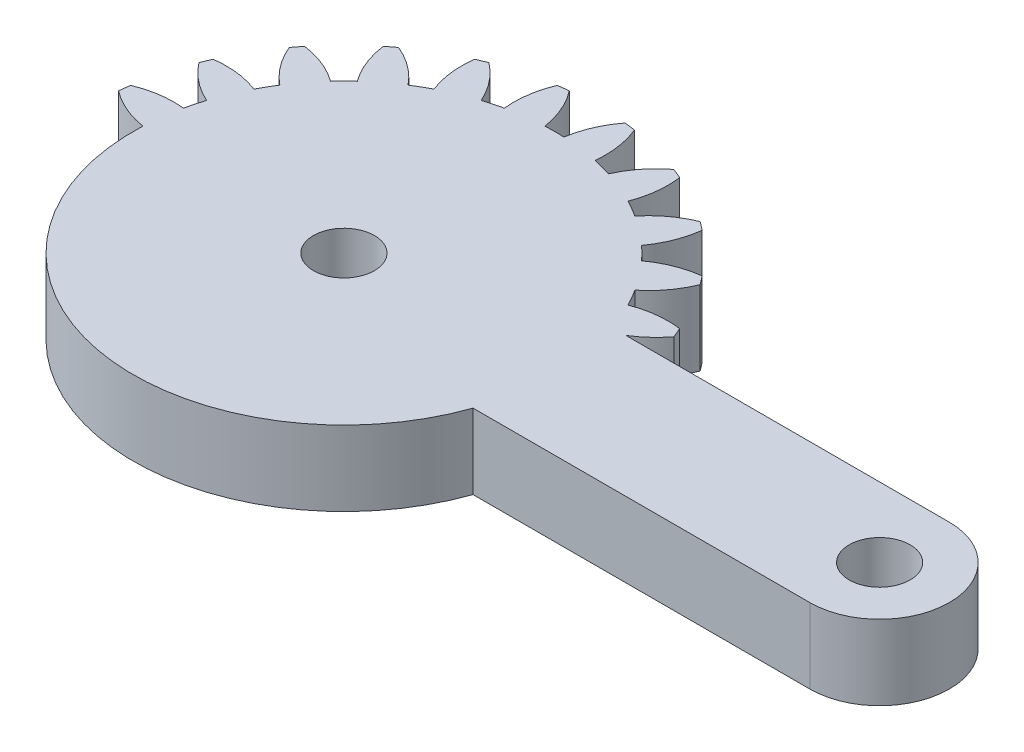
SolidWorks part; units mm, degrees
ref_plane "Front Plane" through (0, 0, 0) normal (0, 0, 1) x (1, 0, 0)
ref_plane "Top Plane" through (0, 0, 0) normal (0, 1, 0) x (1, 0, 0)
ref_plane "Right Plane" through (0, 0, 0) normal (1, 0, 0) x (0, 0, -1)
sketch "Sketch1" plane through (0, 0, 0) normal (0, 1, 0) x (1, 0, 0)
  line L0 (20.6437, 4) -> (2.0816, 4)
  line L1 (2.0816, -4) -> (20.6437, -4)
  arc A0 (2.0816, 4) -> (3.5217, 5.3071) centre (-0.7683, 8.5867) ccw
  arc A1 (3.5217, 5.3071) -> (3.2829, 5.8838) centre (-10.1063, 0) ccw
  arc A2 (3.2829, 5.8838) -> (0.6271, 5.5703) centre (2.5684, 0.5313) ccw
  arc A3 (0.6271, 5.5703) -> (0.0844, 6.5103) centre (-10.1063, 0) ccw
  arc A4 (0.0844, 6.5103) -> (1.6838, 8.6535) centre (-3.3089, 10.711) ccw
  arc A5 (1.6838, 8.6535) -> (1.3038, 9.1487) centre (-10.1063, 0) ccw
  arc A6 (1.3038, 9.1487) -> (-1.1803, 8.1585) centre (1.999, 3.7936) ccw
  arc A7 (-1.1803, 8.1585) -> (-1.9479, 8.926) centre (-10.1063, 0) ccw
  arc A8 (-1.9479, 8.926) -> (-0.9576, 11.4102) centre (-6.3127, 12.1053) ccw
  arc A9 (-0.9576, 11.4102) -> (-1.4528, 11.7901) centre (-10.1063, 0) ccw
  arc A10 (-1.4528, 11.7901) -> (-3.596, 10.1907) centre (0.6046, 6.7975) ccw
  arc A11 (-3.596, 10.1907) -> (-4.5361, 10.7334) centre (-10.1063, 0) ccw
  arc A12 (-4.5361, 10.7334) -> (-4.2225, 13.3892) centre (-9.5751, 12.6747) ccw
  arc A13 (-4.2225, 13.3892) -> (-4.7992, 13.6281) centre (-10.1063, 0) ccw
  arc A14 (-4.7992, 13.6281) -> (-6.4554, 11.5285) centre (-1.5196, 9.3381) ccw
  arc A15 (-6.4554, 11.5285) -> (-7.5039, 11.8094) centre (-10.1063, 0) ccw
  arc A16 (-7.5039, 11.8094) -> (-7.8884, 14.4558) centre (-12.8736, 12.3803) ccw
  arc A17 (-7.8884, 14.4558) -> (-8.5072, 14.5373) centre (-10.1063, 0) ccw
  arc A18 (-8.5072, 14.5373) -> (-9.5636, 12.0806) centre (-4.2291, 11.2423) ccw
  arc A19 (-9.5636, 12.0806) -> (-10.6491, 12.0806) centre (-10.1063, 0) ccw
  arc A20 (-10.6491, 12.0806) -> (-11.7054, 14.5373) centre (-15.9836, 11.2423) ccw
  arc A21 (-11.7054, 14.5373) -> (-12.3243, 14.4558) centre (-10.1063, 0) ccw
  arc A22 (-12.3243, 14.4558) -> (-12.7088, 11.8094) centre (-7.3391, 12.3803) ccw
  arc A23 (-12.7088, 11.8094) -> (-13.7573, 11.5285) centre (-10.1063, 0) ccw
  arc A24 (-13.7573, 11.5285) -> (-15.4135, 13.6281) centre (-18.6931, 9.3381) ccw
  arc A25 (-15.4135, 13.6281) -> (-15.9901, 13.3892) centre (-10.1063, 0) ccw
  arc A26 (-15.9901, 13.3892) -> (-15.6766, 10.7334) centre (-10.6376, 12.6747) ccw
  arc A27 (-15.6766, 10.7334) -> (-16.6166, 10.1907) centre (-10.1063, 0) ccw
  arc A28 (-16.6166, 10.1907) -> (-18.7599, 11.7901) centre (-20.8173, 6.7975) ccw
  arc A29 (-18.7599, 11.7901) -> (-19.255, 11.4102) centre (-10.1063, 0) ccw
  arc A30 (-19.255, 11.4102) -> (-18.2648, 8.926) centre (-13.9, 12.1053) ccw
  arc A31 (-18.2648, 8.926) -> (-19.0324, 8.1585) centre (-10.1063, 0) ccw
  arc A32 (-19.0324, 8.1585) -> (-21.5165, 9.1487) centre (-22.2117, 3.7936) ccw
  arc A33 (-21.5165, 9.1487) -> (-21.8965, 8.6535) centre (-10.1063, 0) ccw
  arc A34 (-21.8965, 8.6535) -> (-20.2971, 6.5103) centre (-16.9038, 10.711) ccw
  arc A35 (-20.2971, 6.5103) -> (-20.8398, 5.5703) centre (-10.1063, 0) ccw
  arc A36 (-20.8398, 5.5703) -> (-23.4956, 5.8838) centre (-22.7811, 0.5313) ccw
  arc A37 (-23.4956, 5.8838) -> (-23.7344, 5.3071) centre (-10.1063, 0) ccw
  arc A38 (-23.7344, 5.3071) -> (-21.6348, 3.6509) centre (-19.4444, 8.5867) ccw
  arc A39 (-21.6348, 3.6509) -> (-21.9157, 2.6025) centre (-10.1063, 0) ccw
  arc A40 (-21.9157, 2.6025) -> (-24.5622, 2.2179) centre (-22.4867, -2.7673) ccw
  arc A41 (-24.5622, 2.2179) -> (-24.6437, 1.5991) centre (-10.1063, 0) ccw
  arc A42 (-24.6437, 1.5991) -> (-22.1869, 0.5427) centre (-21.3486, 5.8773) ccw
  arc A43 (-22.1869, 0.5427) -> (-22.1869, -0.5427) centre (-10.1063, 0) ccw
  arc A44 (-22.1869, -0.5427) -> (-24.6437, -1.5991) centre (-21.3486, -5.8773) ccw
  arc A45 (-24.6437, -1.5991) -> (-24.5622, -2.2179) centre (-10.1063, 0) ccw
  arc A46 (-24.5622, -2.2179) -> (-21.9157, -2.6025) centre (-22.4867, 2.7673) ccw
  arc A47 (-21.9157, -2.6025) -> (-21.6348, -3.6509) centre (-10.1063, 0) ccw
  arc A48 (-21.6348, -3.6509) -> (-23.7344, -5.3071) centre (-19.4444, -8.5867) ccw
  arc A49 (-23.7344, -5.3071) -> (-23.4956, -5.8838) centre (-10.1063, 0) ccw
  arc A50 (-23.4956, -5.8838) -> (-20.8398, -5.5703) centre (-22.7811, -0.5313) ccw
  arc A51 (-20.8398, -5.5703) -> (-20.2971, -6.5103) centre (-10.1063, 0) ccw
  arc A52 (-20.2971, -6.5103) -> (-21.8965, -8.6535) centre (-16.9038, -10.711) ccw
  arc A53 (-21.8965, -8.6535) -> (-21.5165, -9.1487) centre (-10.1063, 0) ccw
  arc A54 (-21.5165, -9.1487) -> (-19.0324, -8.1585) centre (-22.2117, -3.7936) ccw
  arc A55 (-19.0324, -8.1585) -> (-18.2648, -8.926) centre (-10.1063, 0) ccw
  arc A56 (-18.2648, -8.926) -> (-19.255, -11.4102) centre (-13.9, -12.1053) ccw
  arc A57 (-19.255, -11.4102) -> (-18.7599, -11.7901) centre (-10.1063, 0) ccw
  arc A58 (-18.7599, -11.7901) -> (-16.6166, -10.1907) centre (-20.8173, -6.7975) ccw
  arc A59 (-16.6166, -10.1907) -> (-15.6766, -10.7334) centre (-10.1063, 0) ccw
  arc A60 (-15.6766, -10.7334) -> (-15.9901, -13.3892) centre (-10.6376, -12.6747) ccw
  arc A61 (-15.9901, -13.3892) -> (-15.4135, -13.6281) centre (-10.1063, 0) ccw
  arc A62 (-15.4135, -13.6281) -> (-13.7573, -11.5285) centre (-18.6931, -9.3381) ccw
  arc A63 (-13.7573, -11.5285) -> (-12.7088, -11.8094) centre (-10.1063, 0) ccw
  arc A64 (-12.7088, -11.8094) -> (-12.3243, -14.4558) centre (-7.3391, -12.3803) ccw
  arc A65 (-12.3243, -14.4558) -> (-11.7054, -14.5373) centre (-10.1063, 0) ccw
  arc A66 (-11.7054, -14.5373) -> (-10.6491, -12.0806) centre (-15.9836, -11.2423) ccw
  arc A67 (-10.6491, -12.0806) -> (-9.5636, -12.0806) centre (-10.1063, 0) ccw
  arc A68 (-9.5636, -12.0806) -> (-8.5072, -14.5373) centre (-4.2291, -11.2423) ccw
  arc A69 (-8.5072, -14.5373) -> (-7.8884, -14.4558) centre (-10.1063, 0) ccw
  arc A70 (-7.8884, -14.4558) -> (-7.5039, -11.8094) centre (-12.8736, -12.3803) ccw
  arc A71 (-7.5039, -11.8094) -> (-6.4554, -11.5285) centre (-10.1063, 0) ccw
  arc A72 (-6.4554, -11.5285) -> (-4.7992, -13.6281) centre (-1.5196, -9.3381) ccw
  arc A73 (-4.7992, -13.6281) -> (-4.2225, -13.3892) centre (-10.1063, 0) ccw
  arc A74 (-4.2225, -13.3892) -> (-4.5361, -10.7334) centre (-9.5751, -12.6747) ccw
  arc A75 (-4.5361, -10.7334) -> (-3.596, -10.1907) centre (-10.1063, 0) ccw
  arc A76 (-3.596, -10.1907) -> (-1.4528, -11.7901) centre (0.6046, -6.7975) ccw
  arc A77 (-1.4528, -11.7901) -> (-0.9576, -11.4102) centre (-10.1063, 0) ccw
  arc A78 (-0.9576, -11.4102) -> (-1.9479, -8.926) centre (-6.3127, -12.1053) ccw
  arc A79 (-1.9479, -8.926) -> (-1.1803, -8.1585) centre (-10.1063, 0) ccw
  arc A80 (-1.1803, -8.1585) -> (1.3038, -9.1487) centre (1.999, -3.7936) ccw
  arc A81 (1.3038, -9.1487) -> (1.6838, -8.6535) centre (-10.1063, 0) ccw
  arc A82 (1.6838, -8.6535) -> (0.0844, -6.5103) centre (-3.3089, -10.711) ccw
  arc A83 (0.0844, -6.5103) -> (0.6271, -5.5703) centre (-10.1063, 0) ccw
  arc A84 (0.6271, -5.5703) -> (3.2829, -5.8838) centre (2.5684, -0.5313) ccw
  arc A85 (3.2829, -5.8838) -> (3.5217, -5.3071) centre (-10.1063, 0) ccw
  arc A86 (3.5217, -5.3071) -> (2.0816, -4) centre (-0.7683, -8.5867) ccw
  arc A87 (20.6437, -4) -> (20.6437, 4) centre (20.6437, 0) ccw
  circle A88 centre (-10.1063, 0) radius 1.75
  circle A89 centre (20.6437, 0) radius 1.75
  point P180 (0, 0)
  dimension "D1" = 3.5
  dimension "D2" = 3.5
  dimension "D3" = 0.6242
  dimension "D4" = 1.0854
  dimension "D5" = 12.0806
extrude "Boss-Extrude1" add sketch "Sketch1" along normal blind 4.3
sketch "Sketch2" plane through (0, 4.3, 0) normal (0, 1, 0) x (1, 0, 0)
  line L0 (2.0816, -4) -> (1.3057, -4)
  line L2 (20.6437, 4) -> (2.0816, 4)
  line L3 (2.0816, -4) -> (20.6437, -4)
  line L4 (20.6437, 4) -> (2.0816, 4)
  line L5 (2.0816, -4) -> (20.6437, -4)
  circle A0 centre (-10.1063, 0) radius 12.0927
  arc A88 (20.6437, -4) -> (20.6437, 4) centre (20.6437, 0) ccw
  arc A89 (2.0816, 4) -> (3.5217, 5.3071) centre (-0.7683, 8.5867) ccw
  arc A90 (3.5217, 5.3071) -> (3.2829, 5.8838) centre (-10.1063, 0) ccw
  arc A91 (3.2829, 5.8838) -> (0.6271, 5.5703) centre (2.5684, 0.5313) ccw
  arc A92 (0.6271, 5.5703) -> (0.0844, 6.5103) centre (-10.1063, 0) ccw
  arc A93 (0.0844, 6.5103) -> (1.6838, 8.6535) centre (-3.3089, 10.711) ccw
  arc A94 (1.6838, 8.6535) -> (1.3038, 9.1487) centre (-10.1063, 0) ccw
  arc A95 (1.3038, 9.1487) -> (-1.1803, 8.1585) centre (1.999, 3.7936) ccw
  arc A96 (-1.1803, 8.1585) -> (-1.9479, 8.926) centre (-10.1063, 0) ccw
  arc A97 (-1.9479, 8.926) -> (-0.9576, 11.4102) centre (-6.3127, 12.1053) ccw
  arc A98 (-0.9576, 11.4102) -> (-1.4528, 11.7901) centre (-10.1063, 0) ccw
  arc A99 (-1.4528, 11.7901) -> (-3.596, 10.1907) centre (0.6046, 6.7975) ccw
  arc A100 (-3.596, 10.1907) -> (-4.5361, 10.7334) centre (-10.1063, 0) ccw
  arc A101 (-4.5361, 10.7334) -> (-4.2225, 13.3892) centre (-9.5751, 12.6747) ccw
  arc A102 (-4.2225, 13.3892) -> (-4.7992, 13.6281) centre (-10.1063, 0) ccw
  arc A103 (-4.7992, 13.6281) -> (-6.4554, 11.5285) centre (-1.5196, 9.3381) ccw
  arc A104 (-6.4554, 11.5285) -> (-7.5039, 11.8094) centre (-10.1063, 0) ccw
  arc A105 (-7.5039, 11.8094) -> (-7.8884, 14.4558) centre (-12.8736, 12.3803) ccw
  arc A106 (-7.8884, 14.4558) -> (-8.5072, 14.5373) centre (-10.1063, 0) ccw
  arc A107 (-8.5072, 14.5373) -> (-9.5636, 12.0806) centre (-4.2291, 11.2423) ccw
  arc A108 (-9.5636, 12.0806) -> (-10.6491, 12.0806) centre (-10.1063, 0) ccw
  arc A109 (-10.6491, 12.0806) -> (-11.7054, 14.5373) centre (-15.9836, 11.2423) ccw
  arc A110 (-11.7054, 14.5373) -> (-12.3243, 14.4558) centre (-10.1063, 0) ccw
  arc A111 (-12.3243, 14.4558) -> (-12.7088, 11.8094) centre (-7.3391, 12.3803) ccw
  arc A112 (-12.7088, 11.8094) -> (-13.7573, 11.5285) centre (-10.1063, 0) ccw
  arc A113 (-13.7573, 11.5285) -> (-15.4135, 13.6281) centre (-18.6931, 9.3381) ccw
  arc A114 (-15.4135, 13.6281) -> (-15.9901, 13.3892) centre (-10.1063, 0) ccw
  arc A115 (-15.9901, 13.3892) -> (-15.6766, 10.7334) centre (-10.6376, 12.6747) ccw
  arc A116 (-15.6766, 10.7334) -> (-16.6166, 10.1907) centre (-10.1063, 0) ccw
  arc A117 (-16.6166, 10.1907) -> (-18.7599, 11.7901) centre (-20.8173, 6.7975) ccw
  arc A118 (-18.7599, 11.7901) -> (-19.255, 11.4102) centre (-10.1063, 0) ccw
  arc A119 (-19.255, 11.4102) -> (-18.2648, 8.926) centre (-13.9, 12.1053) ccw
  arc A120 (-18.2648, 8.926) -> (-19.0324, 8.1585) centre (-10.1063, 0) ccw
  arc A121 (-19.0324, 8.1585) -> (-21.5165, 9.1487) centre (-22.2117, 3.7936) ccw
  arc A122 (-21.5165, 9.1487) -> (-21.8965, 8.6535) centre (-10.1063, 0) ccw
  arc A123 (-21.8965, 8.6535) -> (-20.2971, 6.5103) centre (-16.9038, 10.711) ccw
  arc A124 (-20.2971, 6.5103) -> (-20.8398, 5.5703) centre (-10.1063, 0) ccw
  arc A125 (-20.8398, 5.5703) -> (-23.4956, 5.8838) centre (-22.7811, 0.5313) ccw
  arc A126 (-23.4956, 5.8838) -> (-23.7344, 5.3071) centre (-10.1063, 0) ccw
  arc A127 (-23.7344, 5.3071) -> (-21.6348, 3.6509) centre (-19.4444, 8.5867) ccw
  arc A128 (-21.6348, 3.6509) -> (-21.9157, 2.6025) centre (-10.1063, 0) ccw
  arc A129 (-21.9157, 2.6025) -> (-24.5622, 2.2179) centre (-22.4867, -2.7673) ccw
  arc A130 (-24.5622, 2.2179) -> (-24.6437, 1.5991) centre (-10.1063, 0) ccw
  arc A131 (-24.6437, 1.5991) -> (-22.1869, 0.5427) centre (-21.3486, 5.8773) ccw
  arc A132 (-22.1869, 0.5427) -> (-22.1869, -0.5427) centre (-10.1063, 0) ccw
  arc A133 (-22.1869, -0.5427) -> (-24.6437, -1.5991) centre (-21.3486, -5.8773) ccw
  arc A134 (-24.6437, -1.5991) -> (-24.5622, -2.2179) centre (-10.1063, 0) ccw
  arc A135 (-24.5622, -2.2179) -> (-21.9157, -2.6025) centre (-22.4867, 2.7673) ccw
  arc A136 (-21.9157, -2.6025) -> (-21.6348, -3.6509) centre (-10.1063, 0) ccw
  arc A137 (-21.6348, -3.6509) -> (-23.7344, -5.3071) centre (-19.4444, -8.5867) ccw
  arc A138 (-23.7344, -5.3071) -> (-23.4956, -5.8838) centre (-10.1063, 0) ccw
  arc A139 (-23.4956, -5.8838) -> (-20.8398, -5.5703) centre (-22.7811, -0.5313) ccw
  arc A140 (-20.8398, -5.5703) -> (-20.2971, -6.5103) centre (-10.1063, 0) ccw
  arc A141 (-20.2971, -6.5103) -> (-21.8965, -8.6535) centre (-16.9038, -10.711) ccw
  arc A142 (-21.8965, -8.6535) -> (-21.5165, -9.1487) centre (-10.1063, 0) ccw
  arc A143 (-21.5165, -9.1487) -> (-19.0324, -8.1585) centre (-22.2117, -3.7936) ccw
  arc A144 (-19.0324, -8.1585) -> (-18.2648, -8.926) centre (-10.1063, 0) ccw
  arc A145 (-18.2648, -8.926) -> (-19.255, -11.4102) centre (-13.9, -12.1053) ccw
  arc A146 (-19.255, -11.4102) -> (-18.7599, -11.7901) centre (-10.1063, 0) ccw
  arc A147 (-18.7599, -11.7901) -> (-16.6166, -10.1907) centre (-20.8173, -6.7975) ccw
  arc A148 (-16.6166, -10.1907) -> (-15.6766, -10.7334) centre (-10.1063, 0) ccw
  arc A149 (-15.6766, -10.7334) -> (-15.9901, -13.3892) centre (-10.6376, -12.6747) ccw
  arc A150 (-15.9901, -13.3892) -> (-15.4135, -13.6281) centre (-10.1063, 0) ccw
  arc A151 (-15.4135, -13.6281) -> (-13.7573, -11.5285) centre (-18.6931, -9.3381) ccw
  arc A152 (-13.7573, -11.5285) -> (-12.7088, -11.8094) centre (-10.1063, 0) ccw
  arc A153 (-12.7088, -11.8094) -> (-12.3243, -14.4558) centre (-7.3391, -12.3803) ccw
  arc A154 (-12.3243, -14.4558) -> (-11.7054, -14.5373) centre (-10.1063, 0) ccw
  arc A155 (-11.7054, -14.5373) -> (-10.6491, -12.0806) centre (-15.9836, -11.2423) ccw
  arc A156 (-10.6491, -12.0806) -> (-9.5636, -12.0806) centre (-10.1063, 0) ccw
  arc A157 (-9.5636, -12.0806) -> (-8.5072, -14.5373) centre (-4.2291, -11.2423) ccw
  arc A158 (-8.5072, -14.5373) -> (-7.8884, -14.4558) centre (-10.1063, 0) ccw
  arc A159 (-7.8884, -14.4558) -> (-7.5039, -11.8094) centre (-12.8736, -12.3803) ccw
  arc A160 (-7.5039, -11.8094) -> (-6.4554, -11.5285) centre (-10.1063, 0) ccw
  arc A161 (-6.4554, -11.5285) -> (-4.7992, -13.6281) centre (-1.5196, -9.3381) ccw
  arc A162 (-4.7992, -13.6281) -> (-4.2225, -13.3892) centre (-10.1063, 0) ccw
  arc A163 (-4.2225, -13.3892) -> (-4.5361, -10.7334) centre (-9.5751, -12.6747) ccw
  arc A164 (-4.5361, -10.7334) -> (-3.596, -10.1907) centre (-10.1063, 0) ccw
  arc A165 (-3.596, -10.1907) -> (-1.4528, -11.7901) centre (0.6046, -6.7975) ccw
  arc A166 (-1.4528, -11.7901) -> (-0.9576, -11.4102) centre (-10.1063, 0) ccw
  arc A167 (-0.9576, -11.4102) -> (-1.9479, -8.926) centre (-6.3127, -12.1053) ccw
  arc A168 (-1.9479, -8.926) -> (-1.1803, -8.1585) centre (-10.1063, 0) ccw
  arc A169 (-1.1803, -8.1585) -> (1.3038, -9.1487) centre (1.999, -3.7936) ccw
  arc A170 (1.3038, -9.1487) -> (1.6838, -8.6535) centre (-10.1063, 0) ccw
  arc A171 (1.6838, -8.6535) -> (0.0844, -6.5103) centre (-3.3089, -10.711) ccw
  arc A172 (0.0844, -6.5103) -> (0.6271, -5.5703) centre (-10.1063, 0) ccw
  arc A173 (0.6271, -5.5703) -> (3.2829, -5.8838) centre (2.5684, -0.5313) ccw
  arc A174 (3.2829, -5.8838) -> (3.5217, -5.3071) centre (-10.1063, 0) ccw
  arc A175 (3.5217, -5.3071) -> (2.0816, -4) centre (-0.7683, -8.5867) ccw
  arc A176 (20.6437, -4) -> (20.6437, 4) centre (20.6437, 0) ccw
  arc A177 (2.0816, 4) -> (3.5217, 5.3071) centre (-0.7683, 8.5867) ccw
  arc A178 (3.5217, 5.3071) -> (3.2829, 5.8838) centre (-10.1063, 0) ccw
  arc A179 (3.2829, 5.8838) -> (0.6271, 5.5703) centre (2.5684, 0.5313) ccw
  arc A180 (0.6271, 5.5703) -> (0.0844, 6.5103) centre (-10.1063, 0) ccw
  arc A181 (0.0844, 6.5103) -> (1.6838, 8.6535) centre (-3.3089, 10.711) ccw
  arc A182 (1.6838, 8.6535) -> (1.3038, 9.1487) centre (-10.1063, 0) ccw
  arc A183 (1.3038, 9.1487) -> (-1.1803, 8.1585) centre (1.999, 3.7936) ccw
  arc A184 (-1.1803, 8.1585) -> (-1.9479, 8.926) centre (-10.1063, 0) ccw
  arc A185 (-1.9479, 8.926) -> (-0.9576, 11.4102) centre (-6.3127, 12.1053) ccw
  arc A186 (-0.9576, 11.4102) -> (-1.4528, 11.7901) centre (-10.1063, 0) ccw
  arc A187 (-1.4528, 11.7901) -> (-3.596, 10.1907) centre (0.6046, 6.7975) ccw
  arc A188 (-3.596, 10.1907) -> (-4.5361, 10.7334) centre (-10.1063, 0) ccw
  arc A189 (-4.5361, 10.7334) -> (-4.2225, 13.3892) centre (-9.5751, 12.6747) ccw
  arc A190 (-4.2225, 13.3892) -> (-4.7992, 13.6281) centre (-10.1063, 0) ccw
  arc A191 (-4.7992, 13.6281) -> (-6.4554, 11.5285) centre (-1.5196, 9.3381) ccw
  arc A192 (-6.4554, 11.5285) -> (-7.5039, 11.8094) centre (-10.1063, 0) ccw
  arc A193 (-7.5039, 11.8094) -> (-7.8884, 14.4558) centre (-12.8736, 12.3803) ccw
  arc A194 (-7.8884, 14.4558) -> (-8.5072, 14.5373) centre (-10.1063, 0) ccw
  arc A195 (-8.5072, 14.5373) -> (-9.5636, 12.0806) centre (-4.2291, 11.2423) ccw
  arc A196 (-9.5636, 12.0806) -> (-10.6491, 12.0806) centre (-10.1063, 0) ccw
  arc A197 (-10.6491, 12.0806) -> (-11.7054, 14.5373) centre (-15.9836, 11.2423) ccw
  arc A198 (-11.7054, 14.5373) -> (-12.3243, 14.4558) centre (-10.1063, 0) ccw
  arc A199 (-12.3243, 14.4558) -> (-12.7088, 11.8094) centre (-7.3391, 12.3803) ccw
  arc A200 (-12.7088, 11.8094) -> (-13.7573, 11.5285) centre (-10.1063, 0) ccw
  arc A201 (-13.7573, 11.5285) -> (-15.4135, 13.6281) centre (-18.6931, 9.3381) ccw
  arc A202 (-15.4135, 13.6281) -> (-15.9901, 13.3892) centre (-10.1063, 0) ccw
  arc A203 (-15.9901, 13.3892) -> (-15.6766, 10.7334) centre (-10.6376, 12.6747) ccw
  arc A204 (-15.6766, 10.7334) -> (-16.6166, 10.1907) centre (-10.1063, 0) ccw
  arc A205 (-16.6166, 10.1907) -> (-18.7599, 11.7901) centre (-20.8173, 6.7975) ccw
  arc A206 (-18.7599, 11.7901) -> (-19.255, 11.4102) centre (-10.1063, 0) ccw
  arc A207 (-19.255, 11.4102) -> (-18.2648, 8.926) centre (-13.9, 12.1053) ccw
  arc A208 (-18.2648, 8.926) -> (-19.0324, 8.1585) centre (-10.1063, 0) ccw
  arc A209 (-19.0324, 8.1585) -> (-21.5165, 9.1487) centre (-22.2117, 3.7936) ccw
  arc A210 (-21.5165, 9.1487) -> (-21.8965, 8.6535) centre (-10.1063, 0) ccw
  arc A211 (-21.8965, 8.6535) -> (-20.2971, 6.5103) centre (-16.9038, 10.711) ccw
  arc A212 (-20.2971, 6.5103) -> (-20.8398, 5.5703) centre (-10.1063, 0) ccw
  arc A213 (-20.8398, 5.5703) -> (-23.4956, 5.8838) centre (-22.7811, 0.5313) ccw
  arc A214 (-23.4956, 5.8838) -> (-23.7344, 5.3071) centre (-10.1063, 0) ccw
  arc A215 (-23.7344, 5.3071) -> (-21.6348, 3.6509) centre (-19.4444, 8.5867) ccw
  arc A216 (-21.6348, 3.6509) -> (-21.9157, 2.6025) centre (-10.1063, 0) ccw
  arc A217 (-21.9157, 2.6025) -> (-24.5622, 2.2179) centre (-22.4867, -2.7673) ccw
  arc A218 (-24.5622, 2.2179) -> (-24.6437, 1.5991) centre (-10.1063, 0) ccw
  arc A219 (-24.6437, 1.5991) -> (-22.1869, 0.5427) centre (-21.3486, 5.8773) ccw
  arc A220 (-22.1869, 0.5427) -> (-22.1869, -0.5427) centre (-10.1063, 0) ccw
  arc A221 (-22.1869, -0.5427) -> (-24.6437, -1.5991) centre (-21.3486, -5.8773) ccw
  arc A222 (-24.6437, -1.5991) -> (-24.5622, -2.2179) centre (-10.1063, 0) ccw
  arc A223 (-24.5622, -2.2179) -> (-21.9157, -2.6025) centre (-22.4867, 2.7673) ccw
  arc A224 (-21.9157, -2.6025) -> (-21.6348, -3.6509) centre (-10.1063, 0) ccw
  arc A225 (-21.6348, -3.6509) -> (-23.7344, -5.3071) centre (-19.4444, -8.5867) ccw
  arc A226 (-23.7344, -5.3071) -> (-23.4956, -5.8838) centre (-10.1063, 0) ccw
  arc A227 (-23.4956, -5.8838) -> (-20.8398, -5.5703) centre (-22.7811, -0.5313) ccw
  arc A228 (-20.8398, -5.5703) -> (-20.2971, -6.5103) centre (-10.1063, 0) ccw
  arc A229 (-20.2971, -6.5103) -> (-21.8965, -8.6535) centre (-16.9038, -10.711) ccw
  arc A230 (-21.8965, -8.6535) -> (-21.5165, -9.1487) centre (-10.1063, 0) ccw
  arc A231 (-21.5165, -9.1487) -> (-19.0324, -8.1585) centre (-22.2117, -3.7936) ccw
  arc A232 (-19.0324, -8.1585) -> (-18.2648, -8.926) centre (-10.1063, 0) ccw
  arc A233 (-18.2648, -8.926) -> (-19.255, -11.4102) centre (-13.9, -12.1053) ccw
  arc A234 (-19.255, -11.4102) -> (-18.7599, -11.7901) centre (-10.1063, 0) ccw
  arc A235 (-18.7599, -11.7901) -> (-16.6166, -10.1907) centre (-20.8173, -6.7975) ccw
  arc A236 (-16.6166, -10.1907) -> (-15.6766, -10.7334) centre (-10.1063, 0) ccw
  arc A237 (-15.6766, -10.7334) -> (-15.9901, -13.3892) centre (-10.6376, -12.6747) ccw
  arc A238 (-15.9901, -13.3892) -> (-15.4135, -13.6281) centre (-10.1063, 0) ccw
  arc A239 (-15.4135, -13.6281) -> (-13.7573, -11.5285) centre (-18.6931, -9.3381) ccw
  arc A240 (-13.7573, -11.5285) -> (-12.7088, -11.8094) centre (-10.1063, 0) ccw
  arc A241 (-12.7088, -11.8094) -> (-12.3243, -14.4558) centre (-7.3391, -12.3803) ccw
  arc A242 (-12.3243, -14.4558) -> (-11.7054, -14.5373) centre (-10.1063, 0) ccw
  arc A243 (-11.7054, -14.5373) -> (-10.6491, -12.0806) centre (-15.9836, -11.2423) ccw
  arc A244 (-10.6491, -12.0806) -> (-9.5636, -12.0806) centre (-10.1063, 0) ccw
  arc A245 (-9.5636, -12.0806) -> (-8.5072, -14.5373) centre (-4.2291, -11.2423) ccw
  arc A246 (-8.5072, -14.5373) -> (-7.8884, -14.4558) centre (-10.1063, 0) ccw
  arc A247 (-7.8884, -14.4558) -> (-7.5039, -11.8094) centre (-12.8736, -12.3803) ccw
  arc A248 (-7.5039, -11.8094) -> (-6.4554, -11.5285) centre (-10.1063, 0) ccw
  arc A249 (-6.4554, -11.5285) -> (-4.7992, -13.6281) centre (-1.5196, -9.3381) ccw
  arc A250 (-4.7992, -13.6281) -> (-4.2225, -13.3892) centre (-10.1063, 0) ccw
  arc A251 (-4.2225, -13.3892) -> (-4.5361, -10.7334) centre (-9.5751, -12.6747) ccw
  arc A252 (-4.5361, -10.7334) -> (-3.596, -10.1907) centre (-10.1063, 0) ccw
  arc A253 (-3.596, -10.1907) -> (-1.4528, -11.7901) centre (0.6046, -6.7975) ccw
  arc A254 (-1.4528, -11.7901) -> (-0.9576, -11.4102) centre (-10.1063, 0) ccw
  arc A255 (-0.9576, -11.4102) -> (-1.9479, -8.926) centre (-6.3127, -12.1053) ccw
  arc A256 (-1.9479, -8.926) -> (-1.1803, -8.1585) centre (-10.1063, 0) ccw
  arc A257 (-1.1803, -8.1585) -> (1.3038, -9.1487) centre (1.999, -3.7936) ccw
  arc A258 (1.3038, -9.1487) -> (1.6838, -8.6535) centre (-10.1063, 0) ccw
  arc A259 (1.6838, -8.6535) -> (0.0844, -6.5103) centre (-3.3089, -10.711) ccw
  arc A260 (0.0844, -6.5103) -> (0.6271, -5.5703) centre (-10.1063, 0) ccw
  arc A261 (0.6271, -5.5703) -> (3.2829, -5.8838) centre (2.5684, -0.5313) ccw
  arc A262 (3.2829, -5.8838) -> (3.5217, -5.3071) centre (-10.1063, 0) ccw
  arc A263 (3.5217, -5.3071) -> (2.0816, -4) centre (-0.7683, -8.5867) ccw
  dimension "D1" = 0
extrude "Cut-Extrude1" cut sketch "Sketch2" against normal blind 10 contours A222 A223 A0 A221 | A226 A227 A0 A225 | A230 A231 A0 A229 | A234 A235 A0 A233 | A238 A239 A0 A237 | A242 A243 A0 A241 | A246 A247 A0 A245 | A250 A251 A0 A249 | A254 A255 A0 A253 | A258 A259 A0 A257 | A262 A263 L0 A0 A261 region at (2.066, 4.3, 5.0775) region at (0.3325, 4.3, 8.01) region at (-2.0963, 4.3, 10.4389) region at (-5.071, 4.3, 12.1563) region at (-8.3889, 4.3, 13.0454) region at (-11.8238, 4.3, 13.0454) region at (-15.1417, 4.3, 12.1563) region at (-18.1164, 4.3, 10.4389) region at (-20.5452, 4.3, 8.01) region at (-22.2627, 4.3, 5.0353) region at (-23.1517, 4.3, 1.7175)
